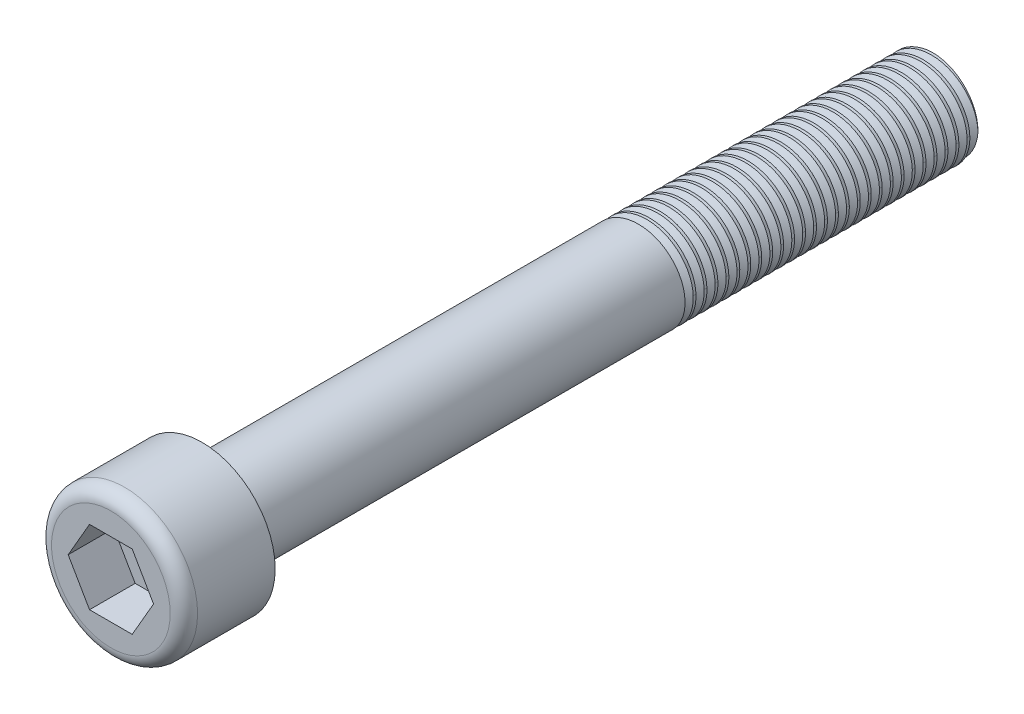
SolidWorks part; units mm, degrees
ref_plane "Front Plane" through (0, 0, 0) normal (0, 0, 1) x (1, 0, 0)
ref_plane "Top Plane" through (0, 0, 0) normal (0, 1, 0) x (1, 0, 0)
ref_plane "Right Plane" through (0, 0, 0) normal (1, 0, 0) x (0, 0, -1)
sketch "Sketch1" plane through (0, 0, 0) normal (0, 0, 1) x (1, 0, 0)
  circle A0 centre (0, 0) radius 8
  dimension "D1" = 16
extrude "Boss-Extrude1" add sketch "Sketch1" along normal blind 10
fillet "Fillet1" radius 1.5 1 edges at (8, 0, 10)
sketch "Sketch2" plane through (0, 0, 10) normal (0, 0, 1) x (1, 0, 0)
  line L1 (4.6765, 0) -> (2.3383, 4.05)
  line L2 (2.3383, 4.05) -> (-2.3383, 4.05)
  line L3 (-2.3383, 4.05) -> (-4.6765, 0)
  line L4 (-4.6765, 0) -> (-2.3383, -4.05)
  line L5 (-2.3383, -4.05) -> (2.3383, -4.05)
  line L6 (2.3383, -4.05) -> (4.6765, 0)
  circle A0 centre (0, 0) radius 4.05 construction
  dimension "D1" = 8.1
extrude "Cut-Extrude1" cut sketch "Sketch2" against normal blind 5
sketch "Sketch3" plane through (0, 0, 5) normal (0, 0, 1) x (1, 0, 0)
  circle A0 centre (0, 0) radius 4.05
sketch "Sketch4" plane through (0, 0, 0) normal (0, 0, -1) x (-1, 0, 0)
  circle A0 centre (0, 0) radius 5
  dimension "D1" = 10
extrude "Boss-Extrude2" add sketch "Sketch4" along normal blind 80
sketch "Sketch5" plane through (0, 0, -80) normal (0, 0, -1) x (-1, 0, 0)
  circle A1 centre (0, 0) radius 5
  circle A2 centre (0, 0) radius 5
  dimension "D1" = 0
curve "Helix/Spiral1" pitch 1.2 height 33 turns 27.5
sketch "Sketch6" plane through (0, 0, 0) normal (1, 0, 0) x (0, 0, -1)
  line L0 (80, 5) -> (80.9, 5)
  line L1 (80.9, 5) -> (80.45, 4.3573)
  line L2 (80.45, 4.3573) -> (80, 5)
  point P3 (80.45, 5)
  dimension "D1" = 0.9
sweep "Cut-Sweep1" cut profiles "Sketch6" path "Helix/Spiral1" align with end faces yes
sketch "Sketch7" plane through (0, 0, 0) normal (-1, 0, 0) x (0, 0, 1)
  line L3 (-47.45, -4.3573) -> (-47.9, -5)
  line L4 (-47.9, -5) -> (-47, -5)
  line L5 (-47, -5) -> (-47.45, -4.3573)
  line L6 (-47.45, -4.3573) -> (-47.9, -5)
  line L7 (-47.9, -5) -> (-47, -5)
  line L8 (-47, -5) -> (-47.45, -4.3573)
  dimension "D1" = 0
extrude "Cut-Extrude2" cut sketch "Sketch7" against normal blind 80
sketch "Sketch8" plane through (0, 0, 5) normal (0, 0, 1) x (1, 0, 0)
  circle A0 centre (0, 0) radius 4.05
